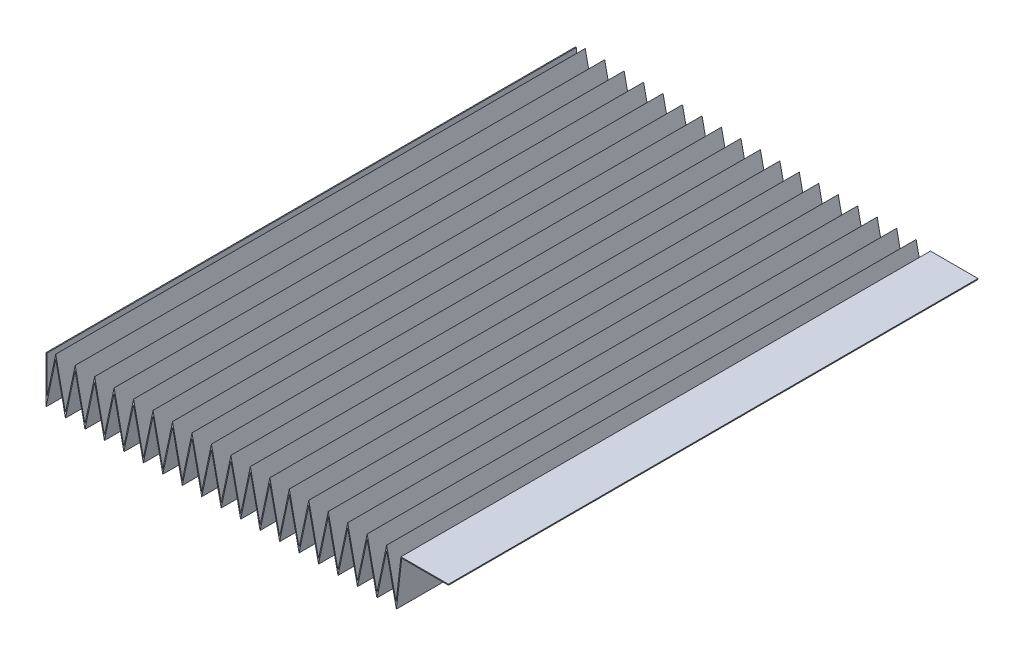
SolidWorks part; units mm, degrees
ref_plane "Front Plane" through (0, 0, 0) normal (0, 0, 1) x (1, 0, 0)
ref_plane "Top Plane" through (0, 0, 0) normal (0, 1, 0) x (1, 0, 0)
ref_plane "Right Plane" through (0, 0, 0) normal (1, 0, 0) x (0, 0, -1)
sketch "Sketch1" plane through (0, 0, 0) normal (0, 0, 1) x (1, 0, 0)
  line L0 (0, 0) -> (3.1246, 14.7732)
  line L1 (3.1246, 14.7732) -> (6.2493, 0)
  line L2 (0, 0) -> (511, 0) construction
  line L3 (6.2493, 0) -> (9.3739, 14.7732)
  line L4 (9.3739, 14.7732) -> (12.4986, 0)
  line L5 (12.4986, 0) -> (15.6232, 14.7732)
  line L6 (15.6232, 14.7732) -> (18.7478, 0)
  line L7 (18.7478, 0) -> (21.8725, 14.7732)
  line L8 (21.8725, 14.7732) -> (24.9971, 0)
  line L9 (24.9971, 0) -> (28.1218, 14.7732)
  line L10 (28.1218, 14.7732) -> (31.2464, 0)
  line L11 (31.2464, 0) -> (34.371, 14.7732)
  line L12 (34.371, 14.7732) -> (37.4957, 0)
  line L13 (37.4957, 0) -> (40.6203, 14.7732)
  line L14 (40.6203, 14.7732) -> (43.745, 0)
  line L15 (43.745, 0) -> (46.8696, 14.7732)
  line L16 (46.8696, 14.7732) -> (49.9942, 0)
  line L17 (49.9942, 0) -> (53.1189, 14.7732)
  line L18 (53.1189, 14.7732) -> (56.2435, 0)
  line L19 (0, 0) -> (0, 15.1)
  line L20 (56.2435, 0) -> (59.3682, 14.7732)
  line L21 (59.3682, 14.7732) -> (62.4928, 0)
  line L22 (62.4928, 0) -> (65.6174, 14.7732)
  line L23 (65.6174, 14.7732) -> (68.7421, 0)
  line L24 (68.7421, 0) -> (71.8667, 14.7732)
  line L25 (71.8667, 14.7732) -> (74.9914, 0)
  line L26 (74.9914, 0) -> (78.116, 14.7732)
  line L27 (78.116, 14.7732) -> (81.2406, 0)
  line L28 (81.2406, 0) -> (84.3653, 14.7732)
  line L29 (84.3653, 14.7732) -> (87.4899, 0)
  line L30 (87.4899, 0) -> (90.6146, 14.7732)
  line L31 (90.6146, 14.7732) -> (93.7392, 0)
  line L32 (93.7392, 0) -> (96.8638, 14.7732)
  line L33 (96.8638, 14.7732) -> (99.9885, 0)
  line L34 (99.9885, 0) -> (103.1131, 14.7732)
  line L35 (103.1131, 14.7732) -> (106.2378, 0)
  line L36 (106.2378, 0) -> (109.3624, 14.7732)
  line L37 (109.3624, 14.7732) -> (112.487, 0)
  line L38 (112.487, 0) -> (114.222, 15)
  line L39 (114.222, 15) -> (129.222, 15)
  line L40 (127.222, 13.6) -> (127.222, 34.6) construction
  point P5 (121.5004, 15)
  dimension "D1" = 511
  dimension "D2" = 15.1
  dimension "D3" = 15
  dimension "D4" = 6.2493
  dimension "D6" = 15
  dimension "D7" = 2
  dimension "D5" = 18
extrude "Extrude-Thin1" add sketch "Sketch1" along normal mid plane 170 thin thin type one direction reverse wall 0.3
